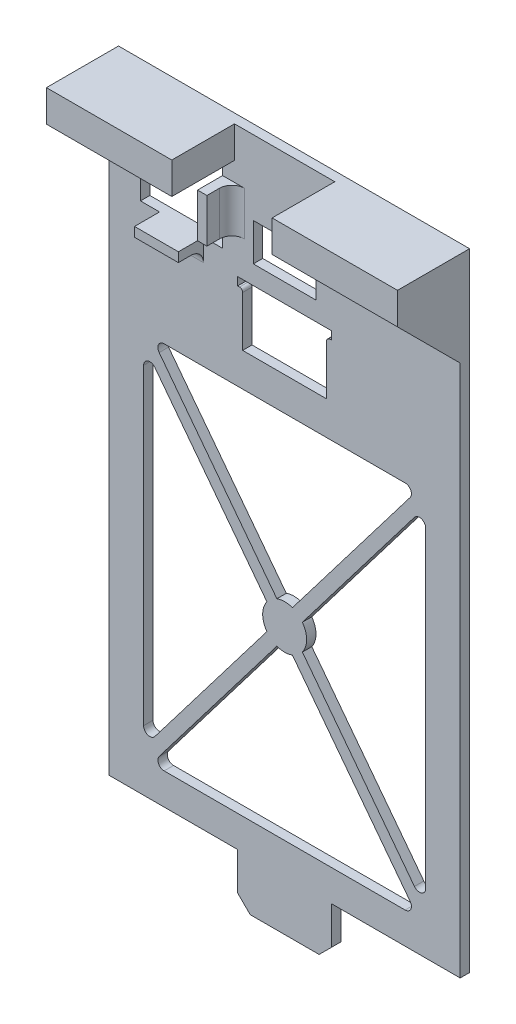
SolidWorks part; units mm, degrees
material "PE Low/Medium Density"
ref_plane "Front Plane" through (0, 0, 0) normal (0, 0, 1) x (1, 0, 0)
ref_plane "Top Plane" through (0, 0, 0) normal (0, 1, 0) x (1, 0, 0)
ref_plane "Right Plane" through (0, 0, 0) normal (1, 0, 0) x (0, 0, -1)
sketch "Sketch1" plane through (0, 0, 0) normal (0, 0, 1) x (1, 0, 0)
  line L0 (28, -2.9) -> (28, -9.4) construction
  line L1 (-28, -6.95) -> (28, -6.95)
  line L2 (-28, -6.95) -> (-28, -106.95)
  line L3 (-28, -106.95) -> (28, -106.95)
  line L4 (28, -6.95) -> (28, -106.95)
  dimension "D1" = 100
extrude "Boss-Extrude1" add sketch "Sketch1" along normal blind 1.5 contours L4 L3 L2 L1
sketch "Sketch2" plane through (0, 0, 1.5) normal (0, 0, 1) x (1, 0, 0)
  line L0 (-10, -12) -> (-23, -12) construction
  line L1 (-28, -6.95) -> (-8, -6.95)
  line L2 (-28, -6.95) -> (-28, -12)
  line L3 (-28, -12) -> (-8, -12)
  line L4 (-8, -6.95) -> (-8, -12)
  line L5 (28, -6.95) -> (8, -6.95)
  line L6 (28, -6.95) -> (28, -12)
  line L7 (28, -12) -> (8, -12)
  line L8 (8, -6.95) -> (8, -12)
  dimension "D1" = 20
extrude "Boss-Extrude2" add sketch "Sketch2" along normal blind 10
sketch "Sketch3" plane through (0, 0, 1.5) normal (0, 0, 1) x (1, 0, 0)
  line L0 (-28, -12) -> (-8, -12) construction
  line L1 (-9.9, -12) -> (-23, -12)
  line L2 (-9.9, -12) -> (-9.9, -25.1)
  line L3 (-9.9, -25.1) -> (-23, -25.1)
  line L4 (-23, -12) -> (-23, -25.1)
  line L6 (-23, -25) -> (-23, -12) construction
  dimension "D1" = 13.1
  dimension "D2" = 13.1
extrude "Cut-Extrude1" cut sketch "Sketch3" against normal through all
sketch "Sketch4" plane through (28, 0, 0) normal (1, 0, 0) x (0, 0, -1)
  line L0 (-11.5, -12) -> (-1.5, -12)
  line L1 (-1.5, -12) -> (-1.5, -22)
  line L2 (-1.5, -12) -> (-1.5, -106.95) construction
  line L3 (-1.5, -22) -> (-11.5, -12)
  dimension "D1" = 45
extrude "Boss-Extrude3" add sketch "Sketch4" against normal blind 5
sketch "Sketch5" plane through (-28, 0, 0) normal (-1, 0, 0) x (0, 0, 1)
  line L4 (1.5, -22) -> (11.5, -12)
  line L5 (11.5, -12) -> (1.5, -12)
  line L6 (1.5, -12) -> (1.5, -22)
  line L7 (1.5, -22) -> (11.5, -12)
  line L8 (11.5, -12) -> (1.5, -12)
  line L9 (1.5, -12) -> (1.5, -22)
  dimension "D1" = 0
extrude "Boss-Extrude4" add sketch "Sketch5" against normal blind 5
sketch "Sketch6" plane through (0, 0, 1.5) normal (0, 0, 1) x (1, 0, 0)
  line L0 (-23, -25.1) -> (-9.9, -25.1) construction
  line L1 (-12.95, -25.1) -> (-19.95, -25.1)
  line L2 (-12.95, -25.1) -> (-12.95, -26.6)
  line L3 (-12.95, -26.6) -> (-19.95, -26.6)
  line L4 (-19.95, -25.1) -> (-19.95, -26.6)
  line L5 (-9.9, -25.1) -> (-9.9, -12) construction
  line L6 (-9.9, -22.05) -> (-8.4, -22.05)
  line L7 (-9.9, -22.05) -> (-9.9, -15.05)
  line L8 (-9.9, -15.05) -> (-8.4, -15.05)
  line L9 (-8.4, -22.05) -> (-8.4, -15.05)
  line L10 (-16.45, -25.1) -> (-16.45, -26.6) construction
  line L11 (-8.4, -18.55) -> (-9.9, -18.55) construction
  dimension "D1" = 1.5
  dimension "D2" = 7
extrude "Boss-Extrude5" add sketch "Sketch6" along normal blind 4
sketch "Sketch7" plane through (0, 0, 1.5) normal (0, 0, 1) x (1, 0, 0)
  line L1 (7.5, -29.1) -> (-7.5, -29.1)
  line L2 (7.5, -29.1) -> (7.5, -27.8)
  line L3 (7.5, -27.8) -> (-7.5, -27.8)
  line L4 (-7.5, -29.1) -> (-7.5, -27.8)
extrude "Cut-Extrude2" cut sketch "Sketch7" against normal through all
sketch "Sketch8" plane through (0, 0, 1.5) normal (0, 0, 1) x (1, 0, 0)
  line L0 (-7.5, -29.1) -> (7.5, -29.1) construction
  line L1 (6.7, -29.1) -> (-6.7, -29.1)
  line L2 (6.7, -29.1) -> (6.7, -37.6)
  line L3 (6.7, -37.6) -> (-6.7, -37.6)
  line L4 (-6.7, -29.1) -> (-6.7, -37.6)
  line L5 (0, -37.6) -> (0, -27.8) construction
  line L6 (7.5, -27.8) -> (-7.5, -27.8) construction
  line L7 (0, -24.8) -> (0, -37.6) construction
  line L8 (5, -24.8) -> (-5, -24.8)
  line L9 (5, -24.8) -> (5, -18.8)
  line L10 (5, -18.8) -> (-5, -18.8)
  line L11 (-5, -24.8) -> (-5, -18.8)
  dimension "D1" = 13.4
  dimension "D2" = 8.5
  dimension "D3" = 10
  dimension "D4" = 6
  dimension "D5" = 3
extrude "Cut-Extrude3" cut sketch "Sketch8" against normal through all
fillet "Fillet1" radius 2 2 edges at (-16.45, -26.6, 1.5) (-8.4, -18.55, 1.5)
sketch "Sketch9" plane through (0, 0, 1.5) normal (0, 0, 1) x (1, 0, 0)
  line L0 (-28, -106.95) -> (28, -106.95) construction
  line L1 (7.5, -106.95) -> (-7.5, -106.95)
  line L2 (7.5, -106.95) -> (7.5, -114.95)
  line L3 (7.5, -114.95) -> (-7.5, -114.95)
  line L4 (-7.5, -106.95) -> (-7.5, -114.95)
  line L5 (0, -114.95) -> (0, -37.6) construction
  line L6 (-6.7, -37.6) -> (6.7, -37.6) construction
  dimension "D1" = 8
  dimension "D2" = 15
extrude "Boss-Extrude6" add sketch "Sketch9" against normal up to surface (1.5 mm away) contours L3 L4 L1 L2 up to face at (0, -21.8, 0)
chamfer "Chamfer1" distance 2 angle 45 2 edges at (7.5, -114.95, 0.75) (-7.5, -114.95, 0.75)
sketch "Sketch10" plane through (0, 0, 1.5) normal (0, 0, 1) x (1, 0, 0)
  line L0 (0, -114.95) -> (0, -101.95) construction
  line L1 (22.5, -101.95) -> (-22.5, -101.95)
  line L2 (22.5, -101.95) -> (22.5, -42.95)
  line L3 (22.5, -42.95) -> (-22.5, -42.95)
  line L4 (-22.5, -101.95) -> (-22.5, -42.95)
  line L5 (5.5, -114.95) -> (-5.5, -114.95) construction
  dimension "D1" = 13
  dimension "D2" = 59
  dimension "D3" = 45
extrude "Cut-Extrude4" cut sketch "Sketch10" against normal blind 4 contours L3 L4 L1 L2
sketch "Sketch11" plane through (0, 0, 1.5) normal (0, 0, 1) x (1, 0, 0)
  line L0 (-22.5, -42.95) -> (22.5, -101.95) construction
  line L1 (-22.5, -101.95) -> (22.5, -42.95) construction
  line L2 (-22.5, -42.95) -> (-21.2423, -42.95)
  line L3 (22.5, -42.95) -> (-22.5, -42.95) construction
  line L4 (-21.2423, -42.95) -> (22.5, -100.3011)
  line L5 (22.5, -101.95) -> (22.5, -42.95) construction
  line L6 (22.5, -100.3011) -> (22.5, -101.95)
  line L7 (22.5, -101.95) -> (21.2423, -101.95)
  line L8 (21.2423, -101.95) -> (-22.5, -44.5989)
  line L9 (-22.5, -101.95) -> (-22.5, -42.95) construction
  line L10 (-22.5, -44.5989) -> (-22.5, -42.95)
  line L11 (22.5, -42.95) -> (21.2423, -42.95)
  line L12 (21.2423, -42.95) -> (-22.5, -100.3011)
  line L13 (-22.5, -100.3011) -> (-22.5, -101.95)
  line L14 (-22.5, -101.95) -> (-21.2423, -101.95)
  line L15 (22.5, -101.95) -> (-22.5, -101.95) construction
  line L16 (-21.2423, -101.95) -> (22.5, -44.5989)
  line L17 (22.5, -44.5989) -> (22.5, -42.95)
  circle A0 centre (0, -72.45) radius 3.5
  line M9 (-22.5, -42.95) -> (22.5, -42.95)
  line M10 (22.5, -42.95) -> (22.5, -101.95)
  line M11 (22.5, -101.95) -> (-22.5, -101.95)
  line M12 (-22.5, -101.95) -> (-22.5, -42.95)
  dimension "D3" = 7
  dimension "D1" = 2
  dimension "D2" = 2
extrude "Boss-Extrude7" add sketch "Sketch11" against normal up to surface (1.5 mm away) contours A0 L4 L8 M9 M12 | A0 L16 L12 M10 M9 | A0 L8 L4 M11 M10 | A0 L12 L16 M12 M11 | L8 A0 L12 | L4 A0 L8 L12 | L12 A0 L16 L8 | L16 A0 L8 | L4 A0 L16 | L8 A0 L4 L16 | L16 A0 L12 L4 | L12 A0 L4 | L8 L16 L4 L12 region at (-12.1383, -56.5308, 1.5) region at (0, -69.6184, 1.5) region at (-1.3883, -70.6922, 1.5) region at (12.1383, -56.5308, 1.5) region at (-2.5973, -72.45, 1.5) region at (-12.1383, -88.3692, 1.5) region at (1.3883, -70.6922, 1.5) region at (0, -72.45, 1.5) region at (-1.3883, -74.2078, 1.5) region at (2.5973, -72.45, 1.5) region at (1.3883, -74.2078, 1.5) region at (0, -75.2816, 1.5) region at (12.1383, -88.3692, 1.5) up to face at (0, -72.45, 0)
fillet "Fillet2" radius 1 8 edges at (-22.5, -100.3011, 0.75) (-21.2423, -101.95, 0.75) (-22.5, -44.5989, 0.75) (-21.2423, -42.95, 0.75) (22.5, -44.5989, 0.75) (21.2423, -42.95, 0.75) (22.5, -100.3011, 0.75) (21.2423, -101.95, 0.75)
fillet "Fillet3" radius 0.5 2 edges at (-6.7, -29.1, 0.75) (6.7, -29.1, 0.75)
